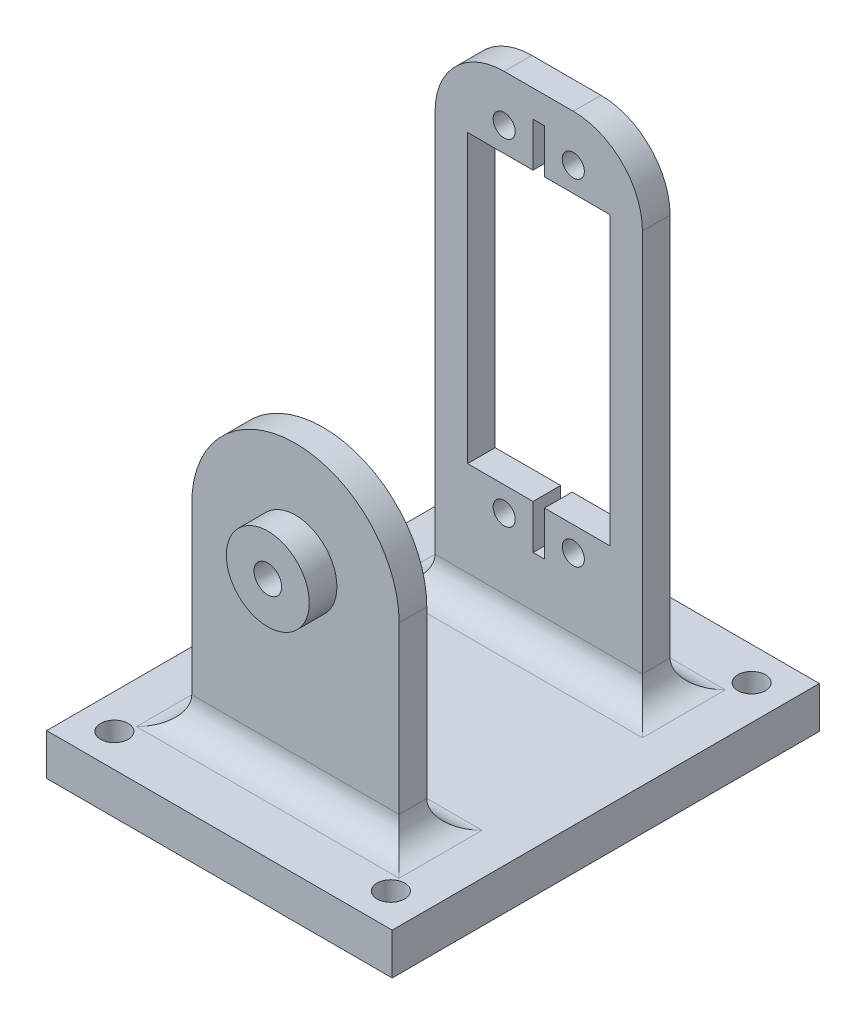
SolidWorks part; units mm, degrees
ref_plane "Front Plane" through (0, 0, 0) normal (0, 0, 1) x (1, 0, 0)
ref_plane "Top Plane" through (0, 0, 0) normal (0, 1, 0) x (1, 0, 0)
ref_plane "Right Plane" through (0, 0, 0) normal (1, 0, 0) x (0, 0, -1)
sketch "Sketch1" plane through (0, 0, 0) normal (0, 0, 1) x (1, 0, 0)
  line L0 (0, 0) -> (0, 53.2406) construction
  line L5 (-15, -28) -> (15, -28)
  line L6 (-15, -28) -> (-15, 31.5)
  line L7 (-5, 41.5) -> (5, 41.5)
  line L8 (15, -28) -> (15, 31.5)
  line L9 (0, 0) -> (15, 0) construction
  line L10 (-10.3, -10.3) -> (-0.83, -10.3)
  line L11 (-10.3, -10.3) -> (-10.3, 31.2)
  line L12 (-10.3, 31.2) -> (-0.83, 31.2)
  line L13 (10.3, -10.3) -> (10.3, 31.2)
  line L15 (-0.83, 31.2) -> (-0.83, 37.6)
  line L16 (-0.83, 37.6) -> (0.83, 37.6)
  line L17 (0.83, 31.2) -> (0.83, 37.6)
  line L18 (-10.3, 10.45) -> (10.3, 10.45) construction
  line L19 (-0.83, -10.3) -> (-0.83, -16.7)
  line L20 (-0.83, -16.7) -> (0.83, -16.7)
  line L21 (0.83, -10.3) -> (0.83, -16.7)
  line L22 (0.83, -10.3) -> (10.3, -10.3)
  line L23 (0.83, 31.2) -> (10.3, 31.2)
  arc A0 (5, 41.5) -> (15, 31.5) centre (5, 31.5) cw
  arc A1 (-15, 31.5) -> (-5, 41.5) centre (-5, 31.5) cw
  circle A2 centre (-5, 34.75) radius 1.6
  circle A3 centre (-5, -13.85) radius 1.6
  circle A4 centre (5, 34.75) radius 1.6
  circle A5 centre (5, -13.85) radius 1.6
  dimension "D4" = 10
  dimension "D10" = 3.2
  dimension "D13" = 3.2
  dimension "D1" = 30
  dimension "D2" = 41.5
  dimension "D3" = 28
  dimension "D5" = 20.6
  dimension "D6" = 31.2
  dimension "D7" = 10.3
  dimension "D8" = 5
  dimension "D9" = 34.75
  dimension "D11" = 5
  dimension "D12" = 13.85
  dimension "D14" = 37.6
  dimension "D15" = 1.66
extrude "Boss-Extrude1" add sketch "Sketch1" along normal blind 4
ref_plane "Plane1" through (0, 0, 39.2) normal (0, 0, 1) x (1, 0, 0)
sketch "Sketch2" plane through (0, 0, 39.2) normal (0, 0, 1) x (1, 0, 0)
  line L0 (0, 0) -> (0, 30.7043) construction
  line L1 (-15, -28) -> (15, -28)
  line L2 (-15, -28) -> (-15, 0)
  line L4 (15, -28) -> (15, 0)
  arc A0 (-15, 0) -> (15, 0) centre (0, 0) cw
  dimension "D1" = 30
  dimension "D3" = 15
  dimension "D2" = 28
extrude "Boss-Extrude2" add sketch "Sketch2" against normal blind 4 separate body
sketch "Sketch3" plane through (0, 0, 39.2) normal (0, 0, 1) x (1, 0, 0)
  circle A0 centre (0, 0) radius 6
  dimension "D1" = 12
extrude "Boss-Extrude3" add sketch "Sketch3" along normal blind 4
sketch "Sketch4" plane through (0, 0, 43.2) normal (0, 0, 1) x (1, 0, 0)
  circle A0 centre (0, 0) radius 2
  dimension "D1" = 4
extrude "Cut-Extrude1" cut sketch "Sketch4" against normal through all
ref_plane "Plane2" through (0, -28, 0) normal (0, 1, 0) x (1, 0, 0)
sketch "Sketch5" plane through (0, -28, 0) normal (0, 1, 0) x (1, 0, 0)
  line L0 (0, 0) -> (0, -51.9066) construction
  line L1 (-25, 11.6) -> (25, 11.6)
  line L2 (-25, 11.6) -> (-25, -50.2)
  line L3 (-25, -50.2) -> (25, -50.2)
  line L4 (25, 11.6) -> (25, -50.2)
  line L5 (-15, 0) -> (15, 0) construction
  line L7 (-16.5, -39.2) -> (16.5, -39.2) construction
  dimension "D2" = 11.6
  dimension "D1" = 50
  dimension "D3" = 11
  dimension "D4" = 61.8
extrude "Boss-Extrude4" add sketch "Sketch5" against normal blind 6
sketch "Sketch6" plane through (0, -34, 0) normal (0, -1, 0) x (1, 0, 0)
  line L0 (-25, 19.3) -> (25, 19.3) construction
  line L1 (-25, -11.6) -> (-25, 50.2) construction
  line L2 (25, 50.2) -> (25, -11.6) construction
  line L3 (0, 50.2) -> (0, -11.6) construction
  line L4 (-25, 50.2) -> (25, 50.2) construction
  line L5 (25, -11.6) -> (-25, -11.6) construction
  circle A0 centre (-20, 45.4) radius 2
  circle A1 centre (20, 45.4) radius 2
  circle A2 centre (20, -6.8) radius 2
  circle A3 centre (-20, -6.8) radius 2
  dimension "D1" = 4
  dimension "D2" = 20
  dimension "D3" = 45.4
extrude "Cut-Extrude2" cut sketch "Sketch6" against normal up to surface (6 mm away) up to face at (0, -28, 2)
fillet "Fillet1" radius 4 8 edges at (0, -28, 39.2) (-15, -28, 37.2) (15, -28, 37.2) (0, -28, 35.2) (15, -28, 2) (0, -28, 4) (-15, -28, 2) (0, -28, 0)
equation "\"L1\"= 120mm'Upper arm"
equation "\"L3\"= 75mm'Wrist→TCP"
equation "\"h0\"= 75mm'Shoulder height"
equation "\"t_link\"= 3mm'Link plate thickness"
equation "\"t_bracket\"= 4mm'Bracket thickness"
equation "\"d_pin\"= 4mm'Pin diameter (M4)"
equation "\"c_fit\"= 0.2mm'Nominal clearance - measured PLA 2026-10-01"
equation "\"L2\"= 120mm'Forearm"
equation "\"c_fit_pivot\"= \"c_fit\" + 0.05mm'Gripper pivot clearance - chosen 0.25 mm 2026-10-01"
equation "\"d_pin_gripper\"= 3mm'Gripper pivot diameter"
equation "\"w_link\"= 20mm'Link plate depth (bending direction)"
equation "\"w_gap\"= 20mm'Twin-plate gap - provisional, set by elbow servo mount"
equation "\"d_boss\"= 13mm'MG996R output boss dia - from downloaded model, verify with calipers"
equation "\"c_boss\"= 1mm'Radial clearance around servo boss"
equation "\"d_servo_hole\"= \"d_boss\" + 2 * \"c_boss\"'Plate clearance hole for servo boss (15 mm)"
equation "\"t_rim\"= 9.5mm'Min material around servo hole (M3 hole + 3 mm webs each side)"
equation "\"w_link_end\"= \"d_servo_hole\" + 2 * \"t_rim\"'Link plate end width at servo end (34 mm)"
equation "\"d_hole_m3\"= \"d_pin_gripper\" + \"c_fit\"'M3 bolt clearance hole (spacer and adapter bolts)"
equation "\"d_hole_pivot\"= \"d_pin\" + \"c_fit_pivot\"'M4 pivot hole where the pin rotates (4.25 mm)"
equation "\"d_horn\"= 20mm'Horn disc diameter (circular horn) - from MG996R model"
equation "\"t_horn\"= 2.3mm'Horn disc thickness"
equation "\"g_horn\"= 2.2mm'Gap from horn disc to plate 2 inner face - from MockShoulder"
equation "\"d_horn_pocket\"= \"d_horn\" + \"c_fit\"'Adapter pocket for horn disc (20.2 mm)"
equation "\"h_horn_pocket\"= \"g_horn\" + \"t_horn\"'Pocket depth from adapter plate-2 face (4.5 mm)"
equation "\"d_horn_screw_cb\"= 8.5mm'Recess for horn centre-screw head (head is 7.5 mm)"
equation "\"h_horn_screw_cb\"= 2.6mm'Recess depth (head is 2.35 mm tall)"
equation "\"d_adapter\"= 26mm'Horn adapter outer diameter"
equation "\"h_adapter\"= \"w_gap\"'Adapter length, fills the plate gap"
equation "\"t_adapter_floor\"= 2mm'Floor under horn disc that the horn screws pass through"
equation "\"d_horn_screw_hole\"= 2.2mm'Clearance for M2 self-tapper through the floor"
equation "\"r_horn_screw\"= 7mm'Horn screw hole radius (14 mm square pattern)"
equation "\"d_access\"= 4mm'Access bore for the M2 screws from the plate-1 side"
equation "\"d_insert_m3\"= 4mm'Hole for M3 heat-set insert - HZYUEGOU M3 inserts are 4.2 OD, hole 4.0; open to 4.1 if too tight"
equation "\"h_insert_m3\"= 6mm'Insert hole depth"
equation "\"x_adapter_bolt\"= 6mm'Adapter bolt offset from pin, along the arm toward its middle"
equation "\"y_adapter_bolt\"= 5mm'Adapter bolt offset from pin, across the arm (+/-)"
equation "\"d_csk_m3\"= 6.4mm'Countersink diameter in plate 1 for M3 flat head (90 deg)"
equation "\"h_pin_bore\"= 10mm'M4 pin engagement depth in the adapter"
equation "\"c_win\"= 0.3mm'Servo window clearance per side in bracket wall A - starting value, tune after a test print"
equation "\"l_servo\"= 40.9mm'MG996R case length without ears - from the model"
equation "\"w_servo\"= 20mm'MG996R case width - from the model"
equation "\"r_servo_short\"= 10mm'Shaft axis to the short end of the case - from the model"
equation "\"r_servo_long\"= \"l_servo\" - \"r_servo_short\"'Shaft axis to the long end of the case (30.9 mm)"
equation "\"l_ear_holes\"= 48.6mm'MG996R ear hole (keyhole slot) spacing along the case - from the model"
equation "\"w_ear_holes\"= 10mm'MG996R ear hole spacing across the case - from the model"
equation "\"a_ear\"= 8.2mm'Servo ear seating face to plate-2 outer face - from MockShoulder (ear face incl. 0.2 edge round)"
equation "\"l_window\"= \"l_servo\" + 2 * \"c_win\"'Wall A window length (41.5 mm)"
equation "\"w_window\"= \"w_servo\" + 2 * \"c_win\"'Wall A window width (20.6 mm)"
equation "\"g_wall_a\"= \"a_ear\" - \"t_bracket\"'Gap behind wall A to plate 2 (4.4 mm) - ear screw heads sit here"
equation "\"g_wall_b\"= 1mm'Plate 1 outer face to wall B - thrust washer"
equation "\"d_axis_turret\"= 34mm'Shoulder axis to turret mounting face - PLACEHOLDER until the turret is designed"
equation "\"t_foot\"= 6mm'Bracket foot thickness"
equation "\"h_wall_top\"= 41.5mm'Wall A top above the shoulder axis (long-end ear holes + 4 mm)"
equation "\"w_wall\"= 30mm'Bracket wall A and B width"
equation "\"w_foot\"= 50mm'Bracket foot width across the walls"
equation "\"t_boss_b\"= 4mm'Extra thickness of the pin boss on the outside of wall B"
equation "\"d_boss_b\"= 12mm'Pin boss diameter on wall B"
equation "\"D1@Sketch1\"=\"w_wall\""
equation "\"D2@Sketch1\"=\"h_wall_top\""
equation "\"D3@Sketch1\"=\"d_axis_turret\" - \"t_foot\""
equation "\"D5@Sketch1\"=\"w_window\""
equation "\"D6@Sketch1\"=\"r_servo_long\" + \"c_win\""
equation "\"D7@Sketch1\"=\"r_servo_short\" + \"c_win\""
equation "\"D8@Sketch1\"=\"w_ear_holes\"/2"
equation "\"D9@Sketch1\"=\"l_ear_holes\"/2 + \"l_servo\"/2 - \"r_servo_short\""
equation "\"D10@Sketch1\"=\"d_hole_m3\""
equation "\"D11@Sketch1\"= \"w_ear_holes\" / 2"
equation "\"D12@Sketch1\"=\"l_ear_holes\"/2 - (\"l_servo\"/2 - \"r_servo_short\")"
equation "\"D13@Sketch1\"=\"d_hole_m3\""
equation "\"D1@Boss-Extrude1\"=\"t_bracket\""
equation "\"D1@Sketch3\"=\"d_boss_b\""
equation "\"D1@Boss-Extrude3\"=\"t_boss_b\""
equation "\"D1@Sketch4\"=\"d_pin\""
equation "\"D1@Sketch5\"=\"w_foot\""
equation "\"D1@Boss-Extrude4\"=\"t_foot\""
equation "\"D1@Sketch6\"=\"d_insert_m3\""
equation "\"D2@Sketch2\"= \"d_axis_turret\" - \"t_foot\""
equation "\"D1@Plane2\"= \"d_axis_turret\" - \"t_foot\""
equation "\"D1@Plane1\"= \"a_ear\" + 2 * \"t_link\" + \"w_gap\" + \"g_wall_b\""
equation "\"D1@Boss-Extrude2\"= \"t_bracket\""
equation "\"D3@Sketch2\"= \"w_wall\" / 2"
equation "\"r_wall_corner\"= 10mm'Wall A top corner radius"
equation "\"l_notch\"= 6.4mm'Ear rib notch length past each end of the wall A window - from the model"
equation "\"w_notch\"= 1.66mm'Ear rib notch width (1.0 rib + 0.33 each side)"
equation "\"l_foot_back\"= 11.6mm'Bracket foot overhang behind wall A outer face"
equation "\"l_foot_front\"= 11mm'Bracket foot overhang past wall B outer face"
equation "\"w_turret_holes\"= 40mm'Turret bolt pattern across the foot (X)"
equation "\"e_turret_hole\"= 4.8mm'Foot insert hole centre to foot end (2.8 mm plastic with d_insert_m3 = 4.0)"
equation "\"z_wall_b_out\"= \"a_ear\" + 2 * \"t_link\" + \"w_gap\" + \"g_wall_b\" + \"t_bracket\"'Wall B outer face from wall A outer face (39.2 mm)"
equation "\"z_turret_hole\"= \"z_wall_b_out\" + \"l_foot_front\" - \"e_turret_hole\"'Upper foot insert holes from wall A outer face (45.4 mm); lower pair mirrors about the foot centre"
equation "\"r_foot_fillet\"= 4mm'Wall-to-foot fillet radius"
equation "\"D4@Sketch1\"= \"r_wall_corner\""
equation "\"D14@Sketch1\"= \"r_servo_long\" + \"c_win\" + \"l_notch\""
equation "\"D15@Sketch1\"= \"w_notch\""
equation "\"D1@Sketch2\"= \"w_wall\""
equation "\"D2@Sketch5\"= \"l_foot_back\""
equation "\"D3@Sketch5\"= \"l_foot_front\""
equation "\"D2@Sketch6\"= \"w_turret_holes\" / 2"
equation "\"D3@Sketch6\"= \"z_turret_hole\""
equation "\"D1@Fillet1\"= \"r_foot_fillet\""
